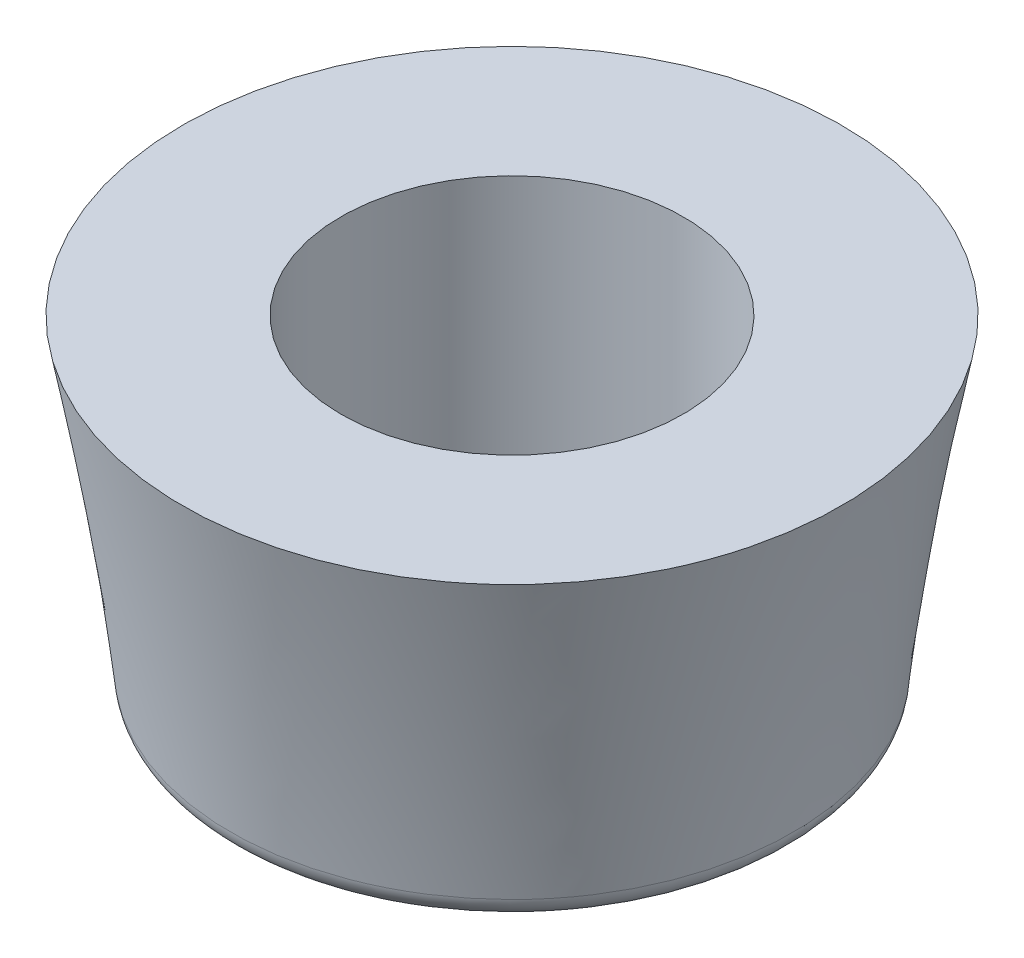
SolidWorks part; units mm, degrees
ref_plane "Front Plane" through (0, 0, 0) normal (0, 0, 1) x (1, 0, 0)
ref_plane "Top Plane" through (0, 0, 0) normal (0, 1, 0) x (1, 0, 0)
ref_plane "Right Plane" through (0, 0, 0) normal (1, 0, 0) x (0, 0, -1)
sketch "Esquisse1" plane through (0, 0, 0) normal (0, 1, 0) x (1, 0, 0)
  circle A0 centre (0, 0) radius 11
  dimension "D1" = 22
ref_plane "Plan1" through (0, 13, 0) normal (0, 1, 0) x (1, 0, 0)
sketch "Esquisse2" plane through (0, 13, 0) normal (0, 1, 0) x (1, 0, 0)
  circle A0 centre (0, 0) radius 13
  dimension "D1" = 26
loft "Lissage1" add profiles "Esquisse2", "Esquisse1" connector at (-10.8068, 13, -7.2258) connector at (-6.6543, 0, -8.759)
fillet "Congé1" radius 1 1 edges at (0, 0, 11)
hole_wizard "Dégagement M121" positions "Esquisse3" profile "Esquisse4" hole size "M12" standard "ISO" end condition through all
sketch "Esquisse3" plane through (0, 13, 0) normal (0, 1, 0) x (1, 0, 0)
  point P0 (0, 0)
sketch "Esquisse4" plane through (0, 13, 0) normal (1, 0, 0) x (0, 0, 1)
  line L0 (0, 0) -> (0, 13)
  line L1 (0, 13) -> (6.75, 13)
  line L2 (6.75, 13) -> (6.75, 0)
  line L5 (6.75, 0) -> (0, 0)
  line L11 (0, -6.35) -> (0, 107.95) construction
  dimension "Diamètre du perçage jusqu'au prochain" = 13.5
  dimension "Profondeur du perçage jusqu'au prochain" = 13
chamfer "Chanfrein1" distance 0.5 angle 45 1 edges at (0, 0, 6.75)
